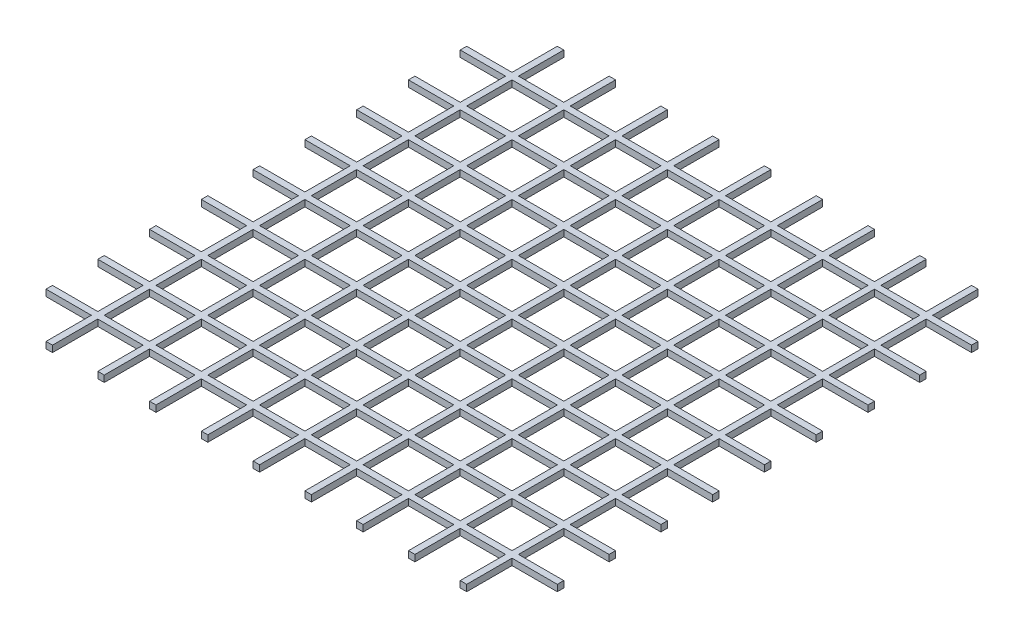
SolidWorks part; units mm, degrees
ref_plane "Front Plane" through (0, 0, 0) normal (0, 0, 1) x (1, 0, 0)
ref_plane "Top Plane" through (0, 0, 0) normal (0, 1, 0) x (1, 0, 0)
ref_plane "Right Plane" through (0, 0, 0) normal (1, 0, 0) x (0, 0, -1)
sketch "Sketch2" plane through (0, 0, 0) normal (0, 1, 0) x (1, 0, 0)
  line L0 (4.5, -0.5) -> (4.5, -4)
  line L3 (0, -40) -> (40, -40)
  line L4 (40, 0) -> (40, -40)
  line L5 (0.5, -0.5) -> (4, -0.5)
  line L6 (0.5, -0.5) -> (0.5, -4)
  line L7 (0.5, -4) -> (4, -4)
  line L8 (4, -0.5) -> (4, -4)
  line L9 (4.5, -0.5) -> (8, -0.5)
  line L10 (8, -0.5) -> (8, -4)
  line L11 (4.5, -4) -> (8, -4)
  line L12 (8.5, -0.5) -> (8.5, -4)
  line L13 (8.5, -0.5) -> (12, -0.5)
  line L14 (12, -0.5) -> (12, -4)
  line L15 (8.5, -4) -> (12, -4)
  line L16 (12.5, -0.5) -> (12.5, -4)
  line L17 (12.5, -0.5) -> (16, -0.5)
  line L18 (16, -0.5) -> (16, -4)
  line L19 (12.5, -4) -> (16, -4)
  line L20 (16.5, -0.5) -> (16.5, -4)
  line L21 (16.5, -0.5) -> (20, -0.5)
  line L22 (20, -0.5) -> (20, -4)
  line L23 (16.5, -4) -> (20, -4)
  line L24 (20.5, -0.5) -> (20.5, -4)
  line L25 (20.5, -0.5) -> (24, -0.5)
  line L26 (24, -0.5) -> (24, -4)
  line L27 (20.5, -4) -> (24, -4)
  line L28 (24.5, -0.5) -> (24.5, -4)
  line L29 (24.5, -0.5) -> (28, -0.5)
  line L30 (28, -0.5) -> (28, -4)
  line L31 (24.5, -4) -> (28, -4)
  line L32 (28.5, -0.5) -> (28.5, -4)
  line L33 (28.5, -0.5) -> (32, -0.5)
  line L34 (32, -0.5) -> (32, -4)
  line L35 (28.5, -4) -> (32, -4)
  line L36 (32.5, -0.5) -> (32.5, -4)
  line L37 (32.5, -0.5) -> (36, -0.5)
  line L38 (36, -0.5) -> (36, -4)
  line L39 (32.5, -4) -> (36, -4)
  line L40 (36.5, -0.5) -> (36.5, -4)
  line L41 (36.5, -0.5) -> (40, -0.5)
  line L42 (40, -0.5) -> (40, -4)
  line L43 (36.5, -4) -> (40, -4)
  line L44 (0.5, -4.5) -> (0.5, -8)
  line L45 (0.5, -4.5) -> (4, -4.5)
  line L46 (4, -4.5) -> (4, -8)
  line L47 (0.5, -8) -> (4, -8)
  line L48 (36.5, -4.5) -> (36.5, -8)
  line L49 (36.5, -8) -> (40, -8)
  line L50 (40, -4.5) -> (40, -8)
  line L51 (36.5, -4.5) -> (40, -4.5)
  line L52 (32.5, -4.5) -> (32.5, -8)
  line L53 (32.5, -8) -> (36, -8)
  line L54 (36, -4.5) -> (36, -8)
  line L55 (32.5, -4.5) -> (36, -4.5)
  line L56 (28.5, -4.5) -> (28.5, -8)
  line L57 (28.5, -8) -> (32, -8)
  line L58 (32, -4.5) -> (32, -8)
  line L59 (28.5, -4.5) -> (32, -4.5)
  line L60 (24.5, -4.5) -> (24.5, -8)
  line L61 (24.5, -8) -> (28, -8)
  line L62 (28, -4.5) -> (28, -8)
  line L63 (24.5, -4.5) -> (28, -4.5)
  line L64 (20.5, -4.5) -> (20.5, -8)
  line L65 (20.5, -8) -> (24, -8)
  line L66 (24, -4.5) -> (24, -8)
  line L67 (20.5, -4.5) -> (24, -4.5)
  line L68 (16.5, -4.5) -> (16.5, -8)
  line L69 (16.5, -8) -> (20, -8)
  line L70 (20, -4.5) -> (20, -8)
  line L71 (16.5, -4.5) -> (20, -4.5)
  line L72 (12.5, -4.5) -> (12.5, -8)
  line L73 (12.5, -8) -> (16, -8)
  line L74 (16, -4.5) -> (16, -8)
  line L75 (12.5, -4.5) -> (16, -4.5)
  line L76 (8.5, -4.5) -> (8.5, -8)
  line L77 (8.5, -8) -> (12, -8)
  line L78 (12, -4.5) -> (12, -8)
  line L79 (8.5, -4.5) -> (12, -4.5)
  line L80 (4.5, -4.5) -> (4.5, -8)
  line L81 (4.5, -8) -> (8, -8)
  line L82 (8, -4.5) -> (8, -8)
  line L83 (4.5, -4.5) -> (8, -4.5)
  line L84 (0.5, -8.5) -> (0.5, -12)
  line L85 (0.5, -8.5) -> (4, -8.5)
  line L86 (4, -8.5) -> (4, -12)
  line L87 (0.5, -12) -> (4, -12)
  line L88 (36.5, -8.5) -> (36.5, -12)
  line L89 (36.5, -12) -> (40, -12)
  line L90 (40, -8.5) -> (40, -12)
  line L91 (36.5, -8.5) -> (40, -8.5)
  line L92 (32.5, -8.5) -> (32.5, -12)
  line L93 (32.5, -12) -> (36, -12)
  line L94 (36, -8.5) -> (36, -12)
  line L95 (32.5, -8.5) -> (36, -8.5)
  line L96 (28.5, -8.5) -> (28.5, -12)
  line L97 (28.5, -12) -> (32, -12)
  line L98 (32, -8.5) -> (32, -12)
  line L99 (28.5, -8.5) -> (32, -8.5)
  line L100 (24.5, -8.5) -> (24.5, -12)
  line L101 (24.5, -12) -> (28, -12)
  line L102 (28, -8.5) -> (28, -12)
  line L103 (24.5, -8.5) -> (28, -8.5)
  line L104 (20.5, -8.5) -> (20.5, -12)
  line L105 (20.5, -12) -> (24, -12)
  line L106 (24, -8.5) -> (24, -12)
  line L107 (20.5, -8.5) -> (24, -8.5)
  line L108 (16.5, -8.5) -> (16.5, -12)
  line L109 (16.5, -12) -> (20, -12)
  line L110 (20, -8.5) -> (20, -12)
  line L111 (16.5, -8.5) -> (20, -8.5)
  line L112 (12.5, -8.5) -> (12.5, -12)
  line L113 (12.5, -12) -> (16, -12)
  line L114 (16, -8.5) -> (16, -12)
  line L115 (12.5, -8.5) -> (16, -8.5)
  line L116 (8.5, -8.5) -> (8.5, -12)
  line L117 (8.5, -12) -> (12, -12)
  line L118 (12, -8.5) -> (12, -12)
  line L119 (8.5, -8.5) -> (12, -8.5)
  line L120 (4.5, -8.5) -> (4.5, -12)
  line L121 (4.5, -12) -> (8, -12)
  line L122 (8, -8.5) -> (8, -12)
  line L123 (4.5, -8.5) -> (8, -8.5)
  line L124 (0.5, -12.5) -> (0.5, -16)
  line L125 (0.5, -12.5) -> (4, -12.5)
  line L126 (4, -12.5) -> (4, -16)
  line L127 (0.5, -16) -> (4, -16)
  line L128 (36.5, -12.5) -> (36.5, -16)
  line L129 (36.5, -16) -> (40, -16)
  line L130 (40, -12.5) -> (40, -16)
  line L131 (36.5, -12.5) -> (40, -12.5)
  line L132 (32.5, -12.5) -> (32.5, -16)
  line L133 (32.5, -16) -> (36, -16)
  line L134 (36, -12.5) -> (36, -16)
  line L135 (32.5, -12.5) -> (36, -12.5)
  line L136 (28.5, -12.5) -> (28.5, -16)
  line L137 (28.5, -16) -> (32, -16)
  line L138 (32, -12.5) -> (32, -16)
  line L139 (28.5, -12.5) -> (32, -12.5)
  line L140 (24.5, -12.5) -> (24.5, -16)
  line L141 (24.5, -16) -> (28, -16)
  line L142 (28, -12.5) -> (28, -16)
  line L143 (24.5, -12.5) -> (28, -12.5)
  line L144 (20.5, -12.5) -> (20.5, -16)
  line L145 (20.5, -16) -> (24, -16)
  line L146 (24, -12.5) -> (24, -16)
  line L147 (20.5, -12.5) -> (24, -12.5)
  line L148 (16.5, -12.5) -> (16.5, -16)
  line L149 (16.5, -16) -> (20, -16)
  line L150 (20, -12.5) -> (20, -16)
  line L151 (16.5, -12.5) -> (20, -12.5)
  line L152 (12.5, -12.5) -> (12.5, -16)
  line L153 (12.5, -16) -> (16, -16)
  line L154 (16, -12.5) -> (16, -16)
  line L155 (12.5, -12.5) -> (16, -12.5)
  line L156 (8.5, -12.5) -> (8.5, -16)
  line L157 (8.5, -16) -> (12, -16)
  line L158 (12, -12.5) -> (12, -16)
  line L159 (8.5, -12.5) -> (12, -12.5)
  line L160 (4.5, -12.5) -> (4.5, -16)
  line L161 (4.5, -16) -> (8, -16)
  line L162 (8, -12.5) -> (8, -16)
  line L163 (4.5, -12.5) -> (8, -12.5)
  line L164 (0.5, -16.5) -> (0.5, -20)
  line L165 (0.5, -16.5) -> (4, -16.5)
  line L166 (4, -16.5) -> (4, -20)
  line L167 (0.5, -20) -> (4, -20)
  line L168 (36.5, -16.5) -> (36.5, -20)
  line L169 (36.5, -20) -> (40, -20)
  line L170 (40, -16.5) -> (40, -20)
  line L171 (36.5, -16.5) -> (40, -16.5)
  line L172 (32.5, -16.5) -> (32.5, -20)
  line L173 (32.5, -20) -> (36, -20)
  line L174 (36, -16.5) -> (36, -20)
  line L175 (32.5, -16.5) -> (36, -16.5)
  line L176 (28.5, -16.5) -> (28.5, -20)
  line L177 (28.5, -20) -> (32, -20)
  line L178 (32, -16.5) -> (32, -20)
  line L179 (28.5, -16.5) -> (32, -16.5)
  line L180 (24.5, -16.5) -> (24.5, -20)
  line L181 (24.5, -20) -> (28, -20)
  line L182 (28, -16.5) -> (28, -20)
  line L183 (24.5, -16.5) -> (28, -16.5)
  line L184 (20.5, -16.5) -> (20.5, -20)
  line L185 (20.5, -20) -> (24, -20)
  line L186 (24, -16.5) -> (24, -20)
  line L187 (20.5, -16.5) -> (24, -16.5)
  line L188 (16.5, -16.5) -> (16.5, -20)
  line L189 (16.5, -20) -> (20, -20)
  line L190 (20, -16.5) -> (20, -20)
  line L191 (16.5, -16.5) -> (20, -16.5)
  line L192 (12.5, -16.5) -> (12.5, -20)
  line L193 (12.5, -20) -> (16, -20)
  line L194 (16, -16.5) -> (16, -20)
  line L195 (12.5, -16.5) -> (16, -16.5)
  line L196 (8.5, -16.5) -> (8.5, -20)
  line L197 (8.5, -20) -> (12, -20)
  line L198 (12, -16.5) -> (12, -20)
  line L199 (8.5, -16.5) -> (12, -16.5)
  line L200 (4.5, -16.5) -> (4.5, -20)
  line L201 (4.5, -20) -> (8, -20)
  line L202 (8, -16.5) -> (8, -20)
  line L203 (4.5, -16.5) -> (8, -16.5)
  line L204 (0.5, -20.5) -> (0.5, -24)
  line L205 (0.5, -20.5) -> (4, -20.5)
  line L206 (4, -20.5) -> (4, -24)
  line L207 (0.5, -24) -> (4, -24)
  line L208 (36.5, -20.5) -> (36.5, -24)
  line L209 (36.5, -24) -> (40, -24)
  line L210 (40, -20.5) -> (40, -24)
  line L211 (36.5, -20.5) -> (40, -20.5)
  line L212 (32.5, -20.5) -> (32.5, -24)
  line L213 (32.5, -24) -> (36, -24)
  line L214 (36, -20.5) -> (36, -24)
  line L215 (32.5, -20.5) -> (36, -20.5)
  line L216 (28.5, -20.5) -> (28.5, -24)
  line L217 (28.5, -24) -> (32, -24)
  line L218 (32, -20.5) -> (32, -24)
  line L219 (28.5, -20.5) -> (32, -20.5)
  line L220 (24.5, -20.5) -> (24.5, -24)
  line L221 (24.5, -24) -> (28, -24)
  line L222 (28, -20.5) -> (28, -24)
  line L223 (24.5, -20.5) -> (28, -20.5)
  line L224 (20.5, -20.5) -> (20.5, -24)
  line L225 (20.5, -24) -> (24, -24)
  line L226 (24, -20.5) -> (24, -24)
  line L227 (20.5, -20.5) -> (24, -20.5)
  line L228 (16.5, -20.5) -> (16.5, -24)
  line L229 (16.5, -24) -> (20, -24)
  line L230 (20, -20.5) -> (20, -24)
  line L231 (16.5, -20.5) -> (20, -20.5)
  line L232 (12.5, -20.5) -> (12.5, -24)
  line L233 (12.5, -24) -> (16, -24)
  line L234 (16, -20.5) -> (16, -24)
  line L235 (12.5, -20.5) -> (16, -20.5)
  line L236 (8.5, -20.5) -> (8.5, -24)
  line L237 (8.5, -24) -> (12, -24)
  line L238 (12, -20.5) -> (12, -24)
  line L239 (8.5, -20.5) -> (12, -20.5)
  line L240 (4.5, -20.5) -> (4.5, -24)
  line L241 (4.5, -24) -> (8, -24)
  line L242 (8, -20.5) -> (8, -24)
  line L243 (4.5, -20.5) -> (8, -20.5)
  line L244 (0.5, -24.5) -> (0.5, -28)
  line L245 (0.5, -24.5) -> (4, -24.5)
  line L246 (4, -24.5) -> (4, -28)
  line L247 (0.5, -28) -> (4, -28)
  line L248 (36.5, -24.5) -> (36.5, -28)
  line L249 (36.5, -28) -> (40, -28)
  line L250 (40, -24.5) -> (40, -28)
  line L251 (36.5, -24.5) -> (40, -24.5)
  line L252 (32.5, -24.5) -> (32.5, -28)
  line L253 (32.5, -28) -> (36, -28)
  line L254 (36, -24.5) -> (36, -28)
  line L255 (32.5, -24.5) -> (36, -24.5)
  line L256 (28.5, -24.5) -> (28.5, -28)
  line L257 (28.5, -28) -> (32, -28)
  line L258 (32, -24.5) -> (32, -28)
  line L259 (28.5, -24.5) -> (32, -24.5)
  line L260 (24.5, -24.5) -> (24.5, -28)
  line L261 (24.5, -28) -> (28, -28)
  line L262 (28, -24.5) -> (28, -28)
  line L263 (24.5, -24.5) -> (28, -24.5)
  line L264 (20.5, -24.5) -> (20.5, -28)
  line L265 (20.5, -28) -> (24, -28)
  line L266 (24, -24.5) -> (24, -28)
  line L267 (20.5, -24.5) -> (24, -24.5)
  line L268 (16.5, -24.5) -> (16.5, -28)
  line L269 (16.5, -28) -> (20, -28)
  line L270 (20, -24.5) -> (20, -28)
  line L271 (16.5, -24.5) -> (20, -24.5)
  line L272 (12.5, -24.5) -> (12.5, -28)
  line L273 (12.5, -28) -> (16, -28)
  line L274 (16, -24.5) -> (16, -28)
  line L275 (12.5, -24.5) -> (16, -24.5)
  line L276 (8.5, -24.5) -> (8.5, -28)
  line L277 (8.5, -28) -> (12, -28)
  line L278 (12, -24.5) -> (12, -28)
  line L279 (8.5, -24.5) -> (12, -24.5)
  line L280 (4.5, -24.5) -> (4.5, -28)
  line L281 (4.5, -28) -> (8, -28)
  line L282 (8, -24.5) -> (8, -28)
  line L283 (4.5, -24.5) -> (8, -24.5)
  line L284 (0.5, -28.5) -> (0.5, -32)
  line L285 (0.5, -28.5) -> (4, -28.5)
  line L286 (4, -28.5) -> (4, -32)
  line L287 (0.5, -32) -> (4, -32)
  line L288 (36.5, -28.5) -> (36.5, -32)
  line L289 (36.5, -32) -> (40, -32)
  line L290 (40, -28.5) -> (40, -32)
  line L291 (36.5, -28.5) -> (40, -28.5)
  line L292 (32.5, -28.5) -> (32.5, -32)
  line L293 (32.5, -32) -> (36, -32)
  line L294 (36, -28.5) -> (36, -32)
  line L295 (32.5, -28.5) -> (36, -28.5)
  line L296 (28.5, -28.5) -> (28.5, -32)
  line L297 (28.5, -32) -> (32, -32)
  line L298 (32, -28.5) -> (32, -32)
  line L299 (28.5, -28.5) -> (32, -28.5)
  line L300 (24.5, -28.5) -> (24.5, -32)
  line L301 (24.5, -32) -> (28, -32)
  line L302 (28, -28.5) -> (28, -32)
  line L303 (24.5, -28.5) -> (28, -28.5)
  line L304 (20.5, -28.5) -> (20.5, -32)
  line L305 (20.5, -32) -> (24, -32)
  line L306 (24, -28.5) -> (24, -32)
  line L307 (20.5, -28.5) -> (24, -28.5)
  line L308 (16.5, -28.5) -> (16.5, -32)
  line L309 (16.5, -32) -> (20, -32)
  line L310 (20, -28.5) -> (20, -32)
  line L311 (16.5, -28.5) -> (20, -28.5)
  line L312 (12.5, -28.5) -> (12.5, -32)
  line L313 (12.5, -32) -> (16, -32)
  line L314 (16, -28.5) -> (16, -32)
  line L315 (12.5, -28.5) -> (16, -28.5)
  line L316 (8.5, -28.5) -> (8.5, -32)
  line L317 (8.5, -32) -> (12, -32)
  line L318 (12, -28.5) -> (12, -32)
  line L319 (8.5, -28.5) -> (12, -28.5)
  line L320 (4.5, -28.5) -> (4.5, -32)
  line L321 (4.5, -32) -> (8, -32)
  line L322 (8, -28.5) -> (8, -32)
  line L323 (4.5, -28.5) -> (8, -28.5)
  line L324 (0.5, -32.5) -> (0.5, -36)
  line L325 (0.5, -32.5) -> (4, -32.5)
  line L326 (4, -32.5) -> (4, -36)
  line L327 (0.5, -36) -> (4, -36)
  line L328 (36.5, -32.5) -> (36.5, -36)
  line L329 (36.5, -36) -> (40, -36)
  line L330 (40, -32.5) -> (40, -36)
  line L331 (36.5, -32.5) -> (40, -32.5)
  line L332 (32.5, -32.5) -> (32.5, -36)
  line L333 (32.5, -36) -> (36, -36)
  line L334 (36, -32.5) -> (36, -36)
  line L335 (32.5, -32.5) -> (36, -32.5)
  line L336 (28.5, -32.5) -> (28.5, -36)
  line L337 (28.5, -36) -> (32, -36)
  line L338 (32, -32.5) -> (32, -36)
  line L339 (28.5, -32.5) -> (32, -32.5)
  line L340 (24.5, -32.5) -> (24.5, -36)
  line L341 (24.5, -36) -> (28, -36)
  line L342 (28, -32.5) -> (28, -36)
  line L343 (24.5, -32.5) -> (28, -32.5)
  line L344 (20.5, -32.5) -> (20.5, -36)
  line L345 (20.5, -36) -> (24, -36)
  line L346 (24, -32.5) -> (24, -36)
  line L347 (20.5, -32.5) -> (24, -32.5)
  line L348 (16.5, -32.5) -> (16.5, -36)
  line L349 (16.5, -36) -> (20, -36)
  line L350 (20, -32.5) -> (20, -36)
  line L351 (16.5, -32.5) -> (20, -32.5)
  line L352 (12.5, -32.5) -> (12.5, -36)
  line L353 (12.5, -36) -> (16, -36)
  line L354 (16, -32.5) -> (16, -36)
  line L355 (12.5, -32.5) -> (16, -32.5)
  line L356 (8.5, -32.5) -> (8.5, -36)
  line L357 (8.5, -36) -> (12, -36)
  line L358 (12, -32.5) -> (12, -36)
  line L359 (8.5, -32.5) -> (12, -32.5)
  line L360 (4.5, -32.5) -> (4.5, -36)
  line L361 (4.5, -36) -> (8, -36)
  line L362 (8, -32.5) -> (8, -36)
  line L363 (4.5, -32.5) -> (8, -32.5)
  line L364 (0.5, -36.5) -> (0.5, -40)
  line L365 (0.5, -36.5) -> (4, -36.5)
  line L366 (4, -36.5) -> (4, -40)
  line L367 (0.5, -40) -> (4, -40)
  line L368 (36.5, -36.5) -> (36.5, -40)
  line L369 (36.5, -40) -> (40, -40)
  line L370 (40, -36.5) -> (40, -40)
  line L371 (36.5, -36.5) -> (40, -36.5)
  line L372 (32.5, -36.5) -> (32.5, -40)
  line L373 (32.5, -40) -> (36, -40)
  line L374 (36, -36.5) -> (36, -40)
  line L375 (32.5, -36.5) -> (36, -36.5)
  line L376 (28.5, -36.5) -> (28.5, -40)
  line L377 (28.5, -40) -> (32, -40)
  line L378 (32, -36.5) -> (32, -40)
  line L379 (28.5, -36.5) -> (32, -36.5)
  line L380 (24.5, -36.5) -> (24.5, -40)
  line L381 (24.5, -40) -> (28, -40)
  line L382 (28, -36.5) -> (28, -40)
  line L383 (24.5, -36.5) -> (28, -36.5)
  line L384 (20.5, -36.5) -> (20.5, -40)
  line L385 (20.5, -40) -> (24, -40)
  line L386 (24, -36.5) -> (24, -40)
  line L387 (20.5, -36.5) -> (24, -36.5)
  line L388 (16.5, -36.5) -> (16.5, -40)
  line L389 (16.5, -40) -> (20, -40)
  line L390 (20, -36.5) -> (20, -40)
  line L391 (16.5, -36.5) -> (20, -36.5)
  line L392 (12.5, -36.5) -> (12.5, -40)
  line L393 (12.5, -40) -> (16, -40)
  line L394 (16, -36.5) -> (16, -40)
  line L395 (12.5, -36.5) -> (16, -36.5)
  line L396 (8.5, -36.5) -> (8.5, -40)
  line L397 (8.5, -40) -> (12, -40)
  line L398 (12, -36.5) -> (12, -40)
  line L399 (8.5, -36.5) -> (12, -36.5)
  line L400 (4.5, -36.5) -> (4.5, -40)
  line L401 (4.5, -40) -> (8, -40)
  line L402 (8, -36.5) -> (8, -40)
  line L403 (4.5, -36.5) -> (8, -36.5)
  line L409 (0.5, -0.5) -> (40, -0.5)
  line L410 (0.5, -0.5) -> (0.5, -40)
  line L411 (0.5, -40) -> (40, -40)
  line L412 (40, -0.5) -> (40, -40)
  dimension "D5" = 3.5
  dimension "D6" = 3.5
  dimension "D7" = 10
  dimension "D8" = 10
extrude "Boss-Extrude4" add sketch "Sketch2" along normal blind 0.5 contours L7 L410 L45 L46 L47 L85 L86 L87 L125 L126 L127 L165 L166 L167 L205 L206 L207 L245 L246 L247 L285 L286 L287 L325 L326 L327 L365 L366 L3 L400 L403 L402 L396 L399 L398 L392 L395 L394 L388 L391 region at (20.25, 0, 20.25)
